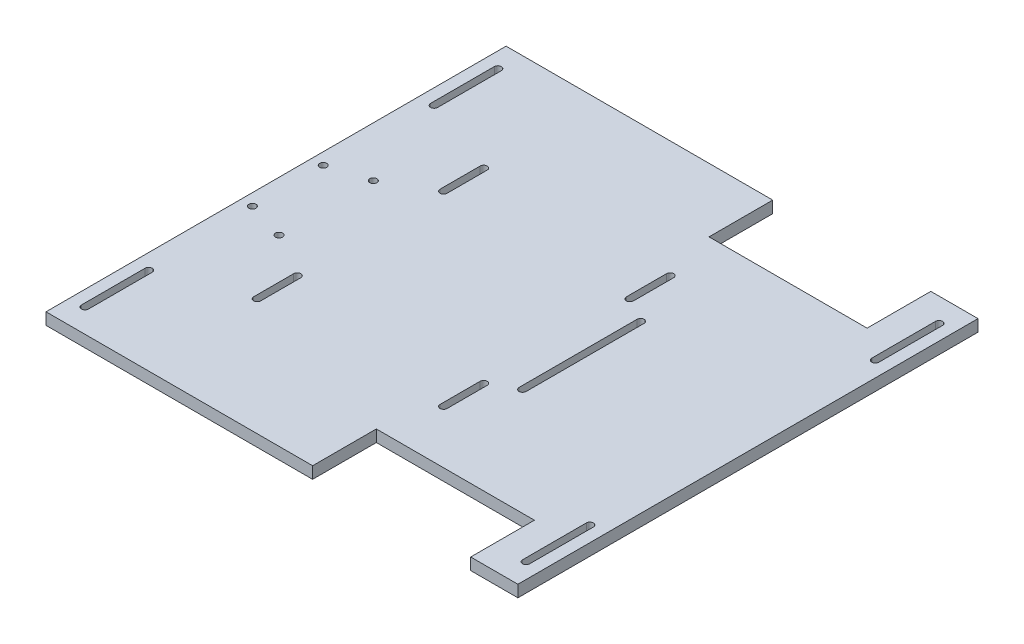
SolidWorks part; units mm, degrees
ref_plane "Front Plane" through (0, 0, 0) normal (0, 0, 1) x (1, 0, 0)
ref_plane "Top Plane" through (0, 0, 0) normal (0, 1, 0) x (1, 0, 0)
ref_plane "Right Plane" through (0, 0, 0) normal (1, 0, 0) x (0, 0, -1)
sketch "Sketch2" plane through (0, 0, 0) normal (0, 1, 0) x (1, 0, 0)
  line L1 (-100, -97.5) -> (100, -97.5)
  line L2 (-100, -97.5) -> (-100, 97.5)
  line L3 (-100, 97.5) -> (100, 97.5)
  line L4 (100, -97.5) -> (100, 97.5)
  line L5 (-100, -97.5) -> (100, 97.5) construction
  line L6 (-100, 97.5) -> (100, -97.5) construction
  point P0 (0, 0)
  dimension "D1" = 200
  dimension "D2" = 195
extrude "Boss-Extrude1" add sketch "Sketch2" along normal blind 5
sketch "Sketch3" plane through (0, 5, 0) normal (0, 1, 0) x (1, 0, 0)
  line L0 (-100, 0) -> (100, 0) construction
  line L1 (-100, 97.5) -> (-100, -97.5) construction
  line L2 (100, -97.5) -> (100, 97.5) construction
  line L3 (0, -97.5) -> (0, 97.5) construction
  line L4 (-100, -97.5) -> (100, -97.5) construction
  line L5 (100, 97.5) -> (-100, 97.5) construction
  line L6 (-93.5, -87.5) -> (-93.5, -60.5) construction
  line L7 (-95, -87.5) -> (-95, -60.5)
  line L8 (-92, -87.5) -> (-92, -60.5)
  line L9 (-93.5, 87.5) -> (-93.5, 60.5) construction
  line L10 (-95, 87.5) -> (-95, 60.5)
  line L11 (-92, 87.5) -> (-92, 60.5)
  line L12 (93.5, 87.5) -> (93.5, 60.5) construction
  line L13 (95, 87.5) -> (95, 60.5)
  line L14 (92, 87.5) -> (92, 60.5)
  line L15 (93.5, -87.5) -> (93.5, -60.5) construction
  line L16 (95, -87.5) -> (95, -60.5)
  line L17 (92, -87.5) -> (92, -60.5)
  arc A0 (-95, -87.5) -> (-92, -87.5) centre (-93.5, -87.5) ccw
  arc A1 (-92, -60.5) -> (-95, -60.5) centre (-93.5, -60.5) ccw
  arc A2 (-95, 87.5) -> (-92, 87.5) centre (-93.5, 87.5) cw
  arc A3 (-92, 60.5) -> (-95, 60.5) centre (-93.5, 60.5) cw
  arc A4 (95, 87.5) -> (92, 87.5) centre (93.5, 87.5) ccw
  arc A5 (92, 60.5) -> (95, 60.5) centre (93.5, 60.5) ccw
  arc A6 (95, -87.5) -> (92, -87.5) centre (93.5, -87.5) cw
  arc A7 (92, -60.5) -> (95, -60.5) centre (93.5, -60.5) cw
  point P14 (-93.5, -74)
  point P21 (-93.5, 74)
  point P28 (93.5, 74)
  point P35 (93.5, -74)
  dimension "D2" = 1.5
  dimension "D3" = 5
  dimension "D4" = 10
  dimension "D1" = 27
extrude "Cut-Extrude1" cut sketch "Sketch3" against normal through all
sketch "Sketch4" plane through (0, 0, 0) normal (0, -1, 0) x (1, 0, 0)
  line L0 (-100, 0) -> (100, 0) construction
  line L1 (-100, -97.5) -> (-100, 97.5) construction
  line L2 (100, 97.5) -> (100, -97.5) construction
  line L3 (100, -97.5) -> (-100, -97.5) construction
  line L4 (13, -97.5) -> (80, -97.5)
  line L5 (13, -97.5) -> (13, -70.5)
  line L6 (13, -70.5) -> (80, -70.5)
  line L7 (80, -97.5) -> (80, -70.5)
  line L8 (80, 97.5) -> (80, 70.5)
  line L9 (13, 97.5) -> (80, 97.5)
  line L10 (13, 70.5) -> (80, 70.5)
  line L11 (13, 97.5) -> (13, 70.5)
  dimension "D1" = 27
  dimension "D2" = 67
  dimension "D3" = 20
extrude "Cut-Extrude2" cut sketch "Sketch4" against normal through all
sketch "Sketch5" plane through (0, 0, 0) normal (0, -1, 0) x (1, 0, 0)
  line L0 (-100, 0) -> (100, 0) construction
  line L1 (-100, -97.5) -> (-100, 97.5) construction
  line L2 (100, 97.5) -> (100, -97.5) construction
  line L3 (13, -70.5) -> (13, -97.5) construction
  line L4 (23, -52) -> (-64, -52)
  line L5 (23, -52) -> (23, 52)
  line L6 (23, 52) -> (-64, 52)
  line L7 (-64, -52) -> (-64, 52)
  line L8 (23, -52) -> (-64, 52) construction
  line L9 (23, 52) -> (-64, -52) construction
  line L10 (-60, -48) -> (-60, -31) construction
  line L11 (-61.5, -48) -> (-61.5, -31)
  line L12 (-58.5, -48) -> (-58.5, -31)
  line L13 (-60, 48) -> (-60, 31) construction
  line L14 (-61.5, 48) -> (-61.5, 31)
  line L15 (-58.5, 48) -> (-58.5, 31)
  line L16 (-20.5, -52) -> (-20.5, 52) construction
  line L17 (19, 48) -> (19, 31) construction
  line L18 (20.5, 48) -> (20.5, 31)
  line L19 (17.5, 48) -> (17.5, 31)
  line L20 (19, -48) -> (19, -31) construction
  line L21 (20.5, -48) -> (20.5, -31)
  line L22 (17.5, -48) -> (17.5, -31)
  arc A0 (-61.5, -48) -> (-58.5, -48) centre (-60, -48) ccw
  arc A1 (-58.5, -31) -> (-61.5, -31) centre (-60, -31) ccw
  arc A2 (-61.5, 48) -> (-58.5, 48) centre (-60, 48) cw
  arc A3 (-58.5, 31) -> (-61.5, 31) centre (-60, 31) cw
  arc A4 (20.5, 48) -> (17.5, 48) centre (19, 48) ccw
  arc A5 (17.5, 31) -> (20.5, 31) centre (19, 31) ccw
  arc A6 (20.5, -48) -> (17.5, -48) centre (19, -48) cw
  arc A7 (17.5, -31) -> (20.5, -31) centre (19, -31) cw
  point P6 (-20.5, 0)
  point P15 (-60, -39.5)
  point P22 (-60, 39.5)
  point P31 (19, 39.5)
  point P38 (19, -39.5)
  dimension "D5" = 1.5
  dimension "D1" = 104
  dimension "D2" = 87
  dimension "D3" = 10
  dimension "D4" = 17
  dimension "D6" = 2.5
  dimension "D7" = 4
extrude "Cut-Extrude4" cut sketch "Sketch5" against normal through all contours L11 A1 L12 A0 | L14 A3 L15 A2 | L19 A5 L18 A4 | L22 A7 L21 A6
sketch "Sketch7" plane through (0, 0, 0) normal (0, -1, 0) x (1, 0, 0)
  line L0 (29.5, -25) -> (29.5, 25) construction
  line L1 (-100, 0) -> (100, 0) construction
  line L2 (28, -25) -> (28, 25)
  line L3 (31, -25) -> (31, 25)
  line L4 (23, -52) -> (23, 52) construction
  arc A0 (28, -25) -> (31, -25) centre (29.5, -25) ccw
  arc A1 (31, 25) -> (28, 25) centre (29.5, 25) ccw
  point P4 (29.5, 0)
  dimension "D2" = 1.5
  dimension "D1" = 50
  dimension "D3" = 5
extrude "Cut-Extrude5" cut sketch "Sketch7" against normal through all
sketch "Sketch8" plane through (0, 5, 0) normal (0, 1, 0) x (1, 0, 0)
  line L0 (-100, 0) -> (100, 0) construction
  line L1 (-100, 97.5) -> (-100, -97.5) construction
  line L2 (100, -97.5) -> (100, 97.5) construction
  line L3 (-78.75, -25) -> (-78.75, 25) construction
  line L4 (-95, -25) -> (-62.5, -25)
  line L5 (-95, -25) -> (-95, 25)
  line L6 (-95, 25) -> (-62.5, 25)
  line L7 (-62.5, -25) -> (-62.5, 25)
  line L8 (-95, -25) -> (-62.5, 25) construction
  line L9 (-95, 25) -> (-62.5, -25) construction
  circle A0 centre (-78.75, -19.995) radius 1.5
  circle A1 centre (-78.75, 19.995) radius 1.5
  point P6 (-78.75, 0)
  dimension "D4" = 3
  dimension "D1" = 32.5
  dimension "D2" = 50
  dimension "D3" = 5
  dimension "D5" = 39.99
extrude "Cut-Extrude6" cut sketch "Sketch8" against normal through all contours A1 | A0 region at (-78.75, 5, -19.995)
sketch "Sketch9" plane through (0, 5, 0) normal (0, 1, 0) x (1, 0, 0)
  line L0 (-100, 0) -> (100, 0) construction
  line L1 (-100, 97.5) -> (-100, -97.5) construction
  line L2 (100, -97.5) -> (100, 97.5) construction
  line L4 (-100, -25) -> (-90, -25)
  line L5 (-100, -25) -> (-100, 25)
  line L6 (-100, 25) -> (-90, 25)
  line L7 (-90, -25) -> (-90, 25)
  line L8 (-100, -25) -> (-90, 25) construction
  line L9 (-100, 25) -> (-90, -25) construction
  circle A0 centre (-95, 15) radius 1.5
  circle A1 centre (-95, -15) radius 1.5
  point P6 (-95, 0)
  dimension "D4" = 3
  dimension "D1" = 10
  dimension "D2" = 0
  dimension "D3" = 50
  dimension "D5" = 30
  dimension "D6" = 5
extrude "Cut-Extrude7" cut sketch "Sketch9" against normal through all contours A0 | A1
